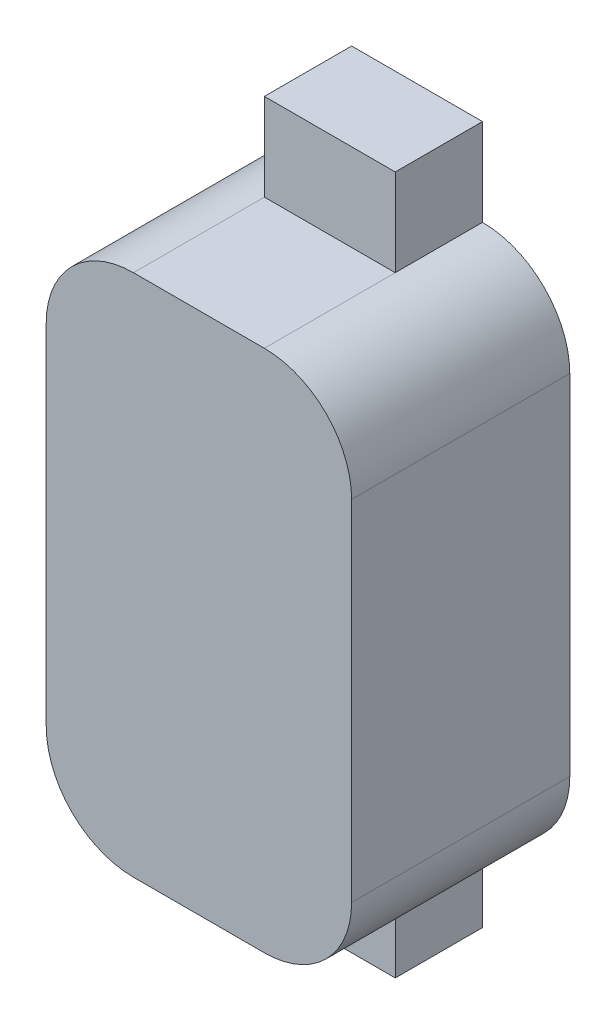
SolidWorks part; units mm, degrees
ref_plane "前视基准面" through (0, 0, 0) normal (0, 0, 1) x (1, 0, 0)
ref_plane "上视基准面" through (0, 0, 0) normal (0, 1, 0) x (1, 0, 0)
ref_plane "右视基准面" through (0, 0, 0) normal (1, 0, 0) x (0, 0, -1)
sketch "草图1" plane through (0, 0, 0) normal (0, 0, 1) x (1, 0, 0)
  line L0 (-2.75, 2) -> (-2.75, -2)
  line L1 (-0.75, 3) -> (0.75, 3)
  line L2 (-1.75, 2) -> (-1.75, -2)
  line L3 (-0.75, -3) -> (0.75, -3)
  line L4 (1.75, 2) -> (1.75, -2)
  line L5 (-1.75, 3) -> (1.75, -3) construction
  line L6 (-1.75, -3) -> (1.75, 3) construction
  line L7 (-0.75, -4) -> (0.75, -4)
  line L8 (2.75, 2) -> (2.75, -2)
  line L9 (-0.75, 4) -> (0.75, 4)
  line L10 (-0.75, 3) -> (-0.75, 4)
  line L11 (0.75, 3) -> (0.75, 4)
  line L12 (-0.75, -4) -> (-0.75, -3)
  line L13 (0.75, -4) -> (0.75, -3)
  line L15 (-1, 2) -> (1, 2)
  line L16 (-1, 2) -> (-1, -2)
  line L17 (-1, -2) -> (1, -2)
  line L18 (1, 2) -> (1, -2)
  line L19 (-1, 2) -> (1, -2) construction
  line L20 (-1, -2) -> (1, 2) construction
  arc A0 (0.75, -3) -> (1.75, -2) centre (0.75, -2) ccw
  arc A1 (-1.75, -2) -> (-0.75, -3) centre (-0.75, -2) ccw
  arc A2 (-0.75, 3) -> (-1.75, 2) centre (-0.75, 2) ccw
  arc A3 (0.75, 3) -> (1.75, 2) centre (0.75, 2) cw
  arc A4 (-2.75, -2) -> (-0.75, -4) centre (-0.75, -2) ccw
  arc A5 (0.75, -4) -> (2.75, -2) centre (0.75, -2) ccw
  arc A6 (0.75, 4) -> (2.75, 2) centre (0.75, 2) cw
  arc A7 (-0.75, 4) -> (-2.75, 2) centre (-0.75, 2) ccw
  point P0 (0, 0)
  point P30 (0, 0)
  dimension "D3" = 1
  dimension "D1" = 6
  dimension "D2" = 3.5
  dimension "D5" = 4
  dimension "D6" = 2
  dimension "D4" = 1
extrude "凸台-拉伸1" add sketch "草图1" along normal blind 2.5 contours L18 L15 L16 L17 | A3 L1 A2 L2 A1 L3 A0 L4 L15 L18 L17 L16 region at (0, 2.9305, 0) region at (0, 0, 0)
extrude "凸台-拉伸2" add sketch "草图1<3>" along normal blind 1 contours L1 L11 L9 L10 | L7 L13 L3 L12 region at (0, 3.5, 0) region at (0, -3.5, 0)
sketch "草图1<3>" plane through (0, 0, 0) normal (0, 0, 1) x (1, 0, 0) same geometry as "草图1"
extrude "切除-拉伸1" cut sketch "草图1<4>" along normal blind 0.7 contours L18 L15 L16 L17 region at (0, 0, 0)
sketch "草图1<4>" plane through (0, 0, 0) normal (0, 0, 1) x (1, 0, 0) same geometry as "草图1"
chamfer "倒角1" distance 0.7 angle 35 4 edges at (0, -2, 0.7) (-1, 0, 0.7) (0, 2, 0.7) (1, 0, 0.7) first distance on face at (0, -2, 0.35) first distance on face at (-1, 0, 0.35) first distance on face at (0, 2, 0.35) first distance on face at (1, 0, 0.35)
